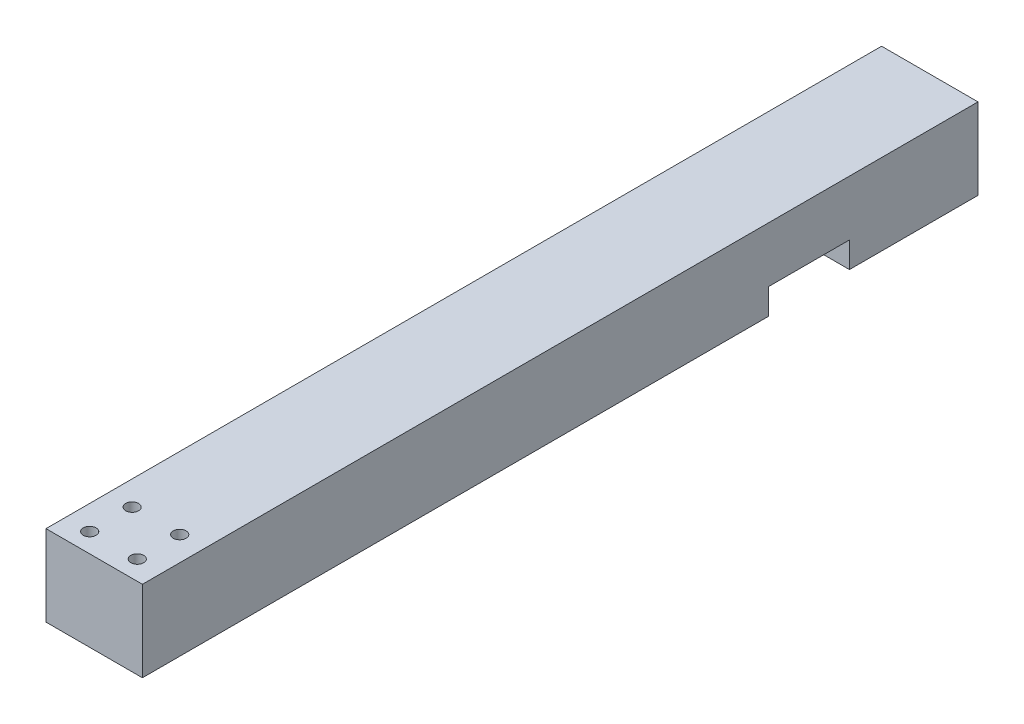
SolidWorks part; units mm, degrees
ref_plane "Front" through (0, 0, 0) normal (0, 0, 1) x (1, 0, 0)
ref_plane "Top" through (0, 0, 0) normal (0, 1, 0) x (1, 0, 0)
ref_plane "Right" through (0, 0, 0) normal (1, 0, 0) x (0, 0, -1)
sketch "Esquisse1" plane through (0, 0, 0) normal (0, 0, 1) x (1, 0, 0)
  line L1 (0, 0) -> (75, 0)
  line L2 (0, 0) -> (0, 63)
  line L3 (0, 63) -> (75, 63)
  line L4 (75, 0) -> (75, 63)
  dimension "D1" = 63
  dimension "D2" = 75
extrude "Boss.-Extru.1" add sketch "Esquisse1" along normal blind 650
sketch "Esquisse2" plane through (0, 0, 0) normal (0, -1, 0) x (1, 0, 0)
  line L0 (19, 650) -> (19, 602) construction
  line L1 (0, 650) -> (75, 650) construction
  line L2 (0, 650) -> (0, 0) construction
  line L3 (37.5, 650) -> (37.5, 937.2696) construction
  circle A0 centre (19, 602) radius 5
  circle A1 centre (19, 635) radius 5
  circle A2 centre (56, 635) radius 5
  circle A3 centre (56, 602) radius 5
  dimension "D1" = 10
  dimension "D2" = 15
  dimension "D4" = 33
  dimension "D3" = 19
extrude "Enlèv. mat.-Extru.1" cut sketch "Esquisse2" against normal through all
sketch "Esquisse3" plane through (0, 0, 0) normal (0, -1, 0) x (1, 0, 0)
  line L0 (0, 650) -> (0, 0) construction
  line L1 (0, 100) -> (75, 100)
  line L2 (0, 100) -> (0, 163)
  line L3 (0, 163) -> (75, 163)
  line L4 (75, 100) -> (75, 163)
  line L5 (75, 650) -> (75, 0) construction
  line L6 (0, 0) -> (75, 0) construction
  dimension "D1" = 63
  dimension "D2" = 100
extrude "Enlèv. mat.-Extru.2" cut sketch "Esquisse3" against normal blind 20
